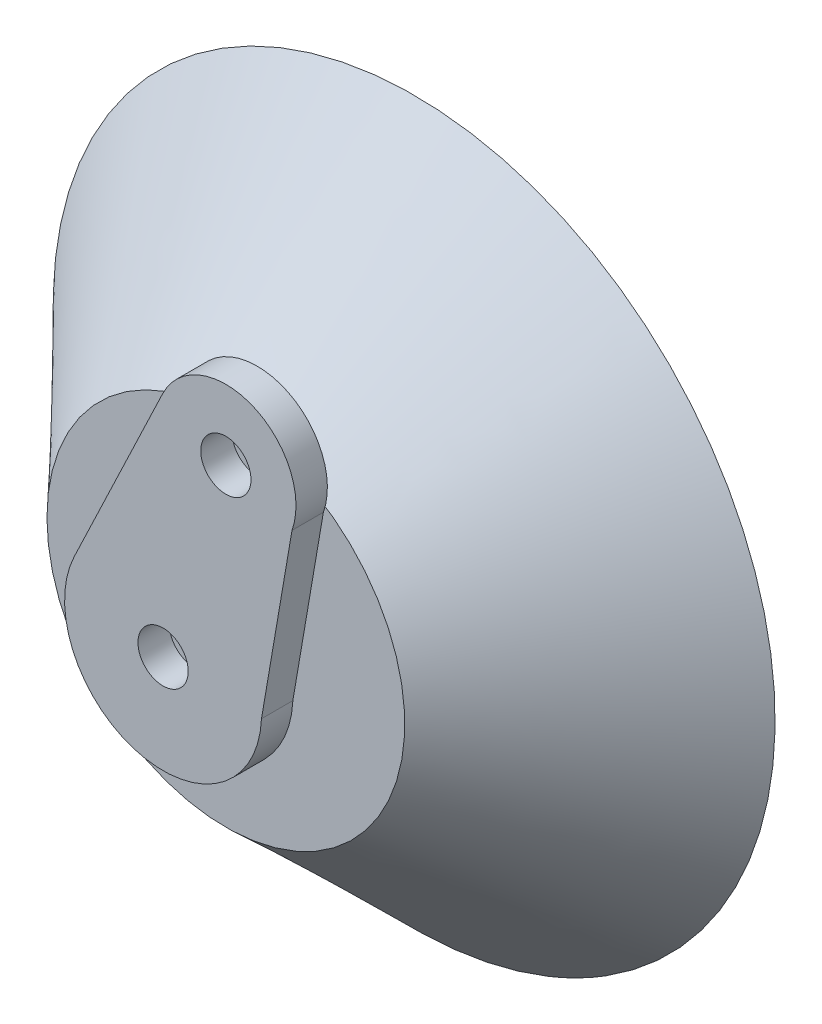
SolidWorks part; units mm, degrees
ref_plane "Front Plane" through (0, 0, 0) normal (0, 0, 1) x (1, 0, 0)
ref_plane "Top Plane" through (0, 0, 0) normal (0, 1, 0) x (1, 0, 0)
ref_plane "Right Plane" through (0, 0, 0) normal (1, 0, 0) x (0, 0, -1)
sketch "Sketch1" plane through (0, 0, 0) normal (0, 0, 1) x (1, 0, 0)
  circle A0 centre (0, 0) radius 57.5
  dimension "D1" = 115
ref_plane "Plane1" through (0, 0, 30) normal (0, 0, 1) x (1, 0, 0)
sketch "Sketch2" plane through (0, 0, 30) normal (0, 0, 1) x (1, 0, 0)
  circle A0 centre (0, 0) radius 28.5
  dimension "D1" = 57
loft "Loft1" add profiles "Sketch1", "Sketch2" connector at (-11.5187, 56.3344, 0) connector at (0.8057, 28.4886, 30)
sketch "Sketch3" plane through (0, 0, 30) normal (0, 0, 1) x (1, 0, 0)
  circle A0 centre (0, 0) radius 10
  dimension "D1" = 20
extrude "Cut-Extrude1" cut sketch "Sketch3" against normal through all
ref_plane "Plane2" through (0, 0, 35) normal (0, 0, 1) x (1, 0, 0)
sketch "Sketch5" plane through (0, 0, 35) normal (0, 0, 1) x (1, 0, 0)
  line L0 (20.5366, 27.7342) -> (15.6741, -0.6862)
  line L1 (-0.0831, 36.2593) -> (-14.1599, 6.7561)
  circle A0 centre (10, 31.4484) radius 4
  arc A1 (20.5366, 27.7342) -> (-0.0831, 36.2593) centre (10, 31.4484) ccw
  arc A2 (-14.1599, 6.7561) -> (15.6741, -0.6862) centre (0, 0) ccw
  circle A3 centre (0, 0) radius 4
  dimension "D1" = 8
  dimension "D2" = 10
  dimension "D3" = 33
extrude "Boss-Extrude1" add sketch "Sketch5" along normal blind 5 separate body
